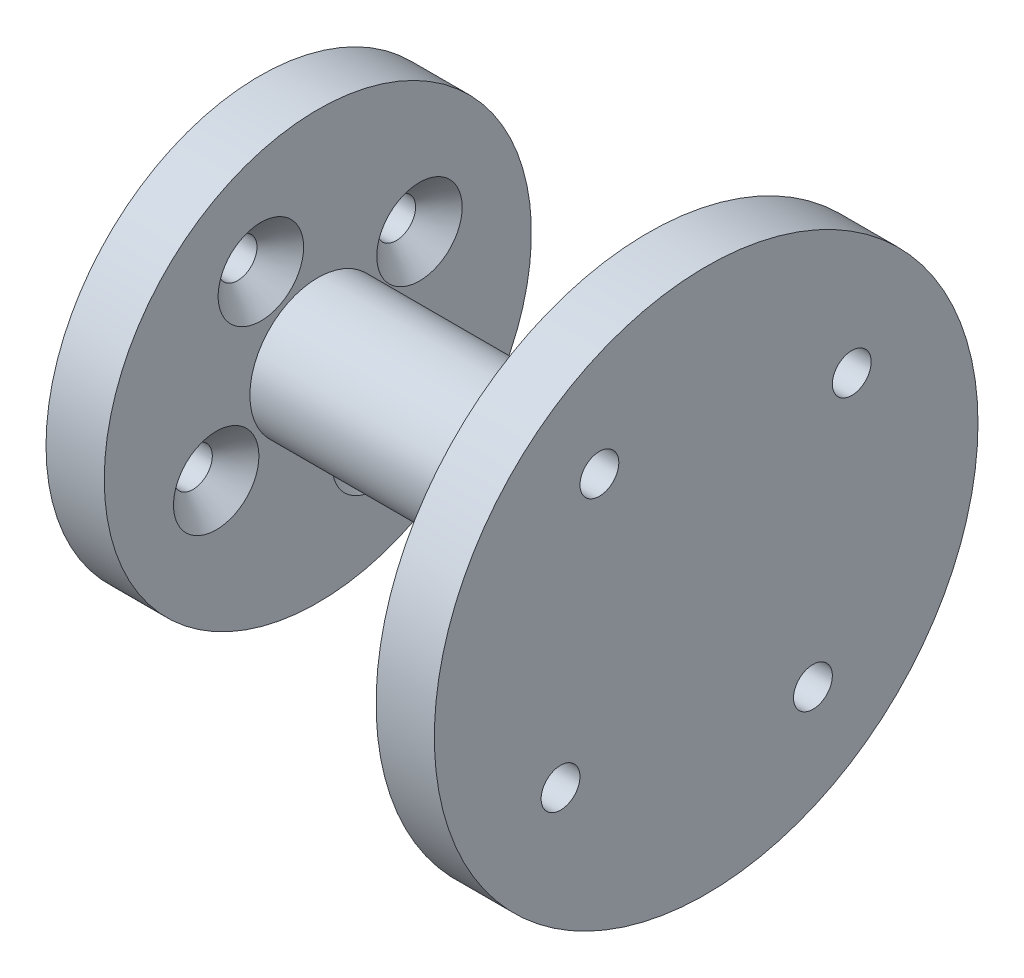
SolidWorks part; units mm, degrees
ref_plane "Спереди" through (0, 0, 0) normal (0, 0, 1) x (1, 0, 0)
ref_plane "Сверху" through (0, 0, 0) normal (0, 1, 0) x (1, 0, 0)
ref_plane "Справа" through (0, 0, 0) normal (1, 0, 0) x (0, 0, -1)
sketch "Эскиз1" plane through (0, 0, 0) normal (0, 0, 1) x (1, 0, 0)
  line L0 (0, 0) -> (100.9242, 0) construction
  line L7 (4, 11) -> (7, 11)
  line L13 (4, 11) -> (4, 0)
  line L14 (4, 0) -> (7, 0)
  line L15 (7, 0) -> (7, 11)
  point P2 (4, 11)
  point P4 (0, 0)
  dimension "D2" = 22
  dimension "D4" = 3
  dimension "D5" = 11
revolve "Повернуть1" add sketch "Эскиз1" angle 360 about L0
hole_wizard "Зенковка для  винта с плоской головкой M22" positions "Эскиз4" profile "Эскиз5" countersink size "M2" standard "Ansi Metric" end condition through all
sketch "Эскиз4" plane through (7, 0, 0) normal (1, 0, 0) x (0, 0, -1)
  point P0 (-2.9334, 5.234)
  dimension "D1" = 6
sketch "Эскиз5" plane through (7, 5.234, 2.9334) normal (0, 1, 0) x (0, 0, -1)
  line L0 (0, 0) -> (0, 3)
  line L1 (0, 3) -> (1, 3)
  line L2 (1, 3) -> (1, 1.2)
  line L3 (1, 1.2) -> (2.2, 0)
  line L5 (2.2, 0) -> (0, 0)
  line L6 (-1, 1.2) -> (-2.2, 0) construction
  line L11 (0, -6.35) -> (0, 107.95) construction
  dimension "Диаметр сквозного отверстия" = 2
  dimension "Глубина сквозного отверстия" = 3
  dimension "Диаметр передней зенковки" = 4.4
  dimension "Угол передней зенковки" = 90
ref_axis "Ось1" through (7, 0, 0) along (-1, 0, 0)
ref_axis "Ось2" through (7, 0, 0) along (-1, 0, 0)
pattern_circular "Круговой массив2" count 4 over 360 about axis through (7, 0, 0) along (-1, 0, 0) of "Зенковка для  винта с плоской головкой M22"
sketch "Эскиз6" plane through (7, 0, 0) normal (1, 0, 0) x (0, 0, -1)
  circle A0 centre (0, 0) radius 3.5
  dimension "D1" = 7
extrude "Бобышка-Вытянуть1" add sketch "Эскиз6" along normal blind 17 contours A0
sketch "Эскиз7" plane through (24, 0, 0) normal (1, 0, 0) x (0, 0, -1)
  circle A0 centre (0, 0) radius 14
  dimension "D1" = 28
extrude "Бобышка-Вытянуть2" add sketch "Эскиз7" along normal blind 3 contours A0
sketch "Эскиз8" plane through (27, 0, 0) normal (1, 0, 0) x (0, 0, -1)
  circle A0 centre (-5.4991, 7.5) radius 1
  dimension "D1" = 2
  dimension "D2" = 9.3
  dimension "D3" = 7.5
extrude "Вырез-Вытянуть1" cut sketch "Эскиз8" against normal up to next contours A0
pattern_circular "Круговой массив3" count 4 over 360 about axis through (7, 0, 0) along (-1, 0, 0) of "Вырез-Вытянуть1"
